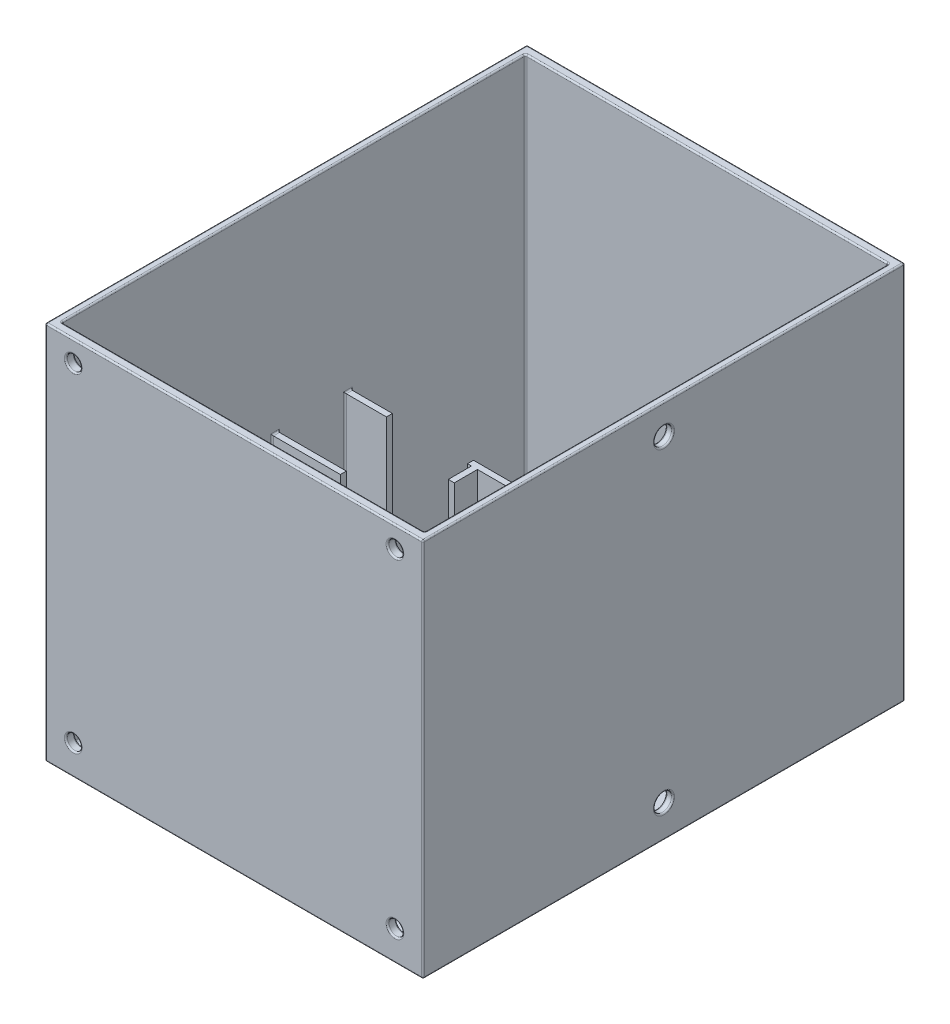
SolidWorks part; units mm, degrees
ref_plane "前视基准面" through (0, 0, 0) normal (0, 0, 1) x (1, 0, 0)
ref_plane "上视基准面" through (0, 0, 0) normal (0, 1, 0) x (1, 0, 0)
ref_plane "右视基准面" through (0, 0, 0) normal (1, 0, 0) x (0, 0, -1)
sketch "草图2" plane through (0, 0, 0) normal (0, 0, 1) x (1, 0, 0)
  line L0 (-53.75, 54.9) -> (53.75, 54.9)
  line L1 (-60.6355, -61.9328) -> (60.6355, -61.9328)
  line L2 (-60.6355, -61.9328) -> (-60.6355, 61.9328)
  line L3 (-60.6355, 61.9328) -> (60.6355, 61.9328)
  line L4 (60.6355, -61.9328) -> (60.6355, 61.9328)
  line L5 (-60.6355, -61.9328) -> (60.6355, 61.9328) construction
  line L6 (-60.6355, 61.9328) -> (60.6355, -61.9328) construction
  line L7 (53.75, 54.9) -> (53.75, -54.9)
  line L8 (53.75, -54.9) -> (-53.75, -54.9)
  line L9 (-53.75, -54.9) -> (-53.75, 54.9)
  circle A0 centre (-53.75, 54.9) radius 2.4552
  circle A1 centre (-53.75, -54.9) radius 2.4552
  circle A2 centre (53.75, 54.9) radius 2.4552
  circle A3 centre (53.75, -54.9) radius 2.4552
  point P0 (0, 0)
  dimension "D1" = 107.5
  dimension "D2" = 54.9
  dimension "D3" = 109.8
  dimension "D4" = 53.75
extrude "凸台-拉伸2" add sketch "草图2" along normal blind 3 contours L1 L4 L3 L2 A3 L8 A1 L9 A0 L0 A2 L7 | A3 L7 A2 L0 A0 L9 A1 L8
sketch "草图4" plane through (0, 0, 0) normal (0, 0, -1) x (-1, 0, 0)
  line L0 (-60.6355, 61.9328) -> (-60.6355, -61.9328)
  line L1 (-60.6355, -61.9328) -> (-63.1355, -61.9328)
  line L2 (-63.1355, -61.9328) -> (-63.1355, 61.9328)
  line L3 (-63.1355, 61.9328) -> (-60.6355, 61.9328)
  dimension "D1" = 2.5
extrude "凸台-拉伸3" add sketch "草图4" along normal blind 155 and the other way blind 3
sketch "草图5" plane through (0, 0, 0) normal (0, 0, -1) x (-1, 0, 0)
  line L0 (60.6355, 61.9328) -> (63.1355, 61.9328)
  line L1 (63.1355, 61.9328) -> (63.1355, -61.9328)
  line L2 (63.1355, -61.9328) -> (60.6355, -61.9328)
  line L3 (60.6355, -61.9328) -> (60.6355, 61.9328)
  dimension "D1" = 2.5
extrude "凸台-拉伸4" add sketch "草图5" along normal blind 155 and the other way blind 3
sketch "草图6" plane through (0, 0, -155) normal (0, 0, -1) x (-1, 0, 0)
  line L1 (-63.1355, 61.9328) -> (63.1355, 61.9328)
  line L2 (-63.1355, 61.9328) -> (-63.1355, -61.9328)
  line L3 (-63.1355, -61.9328) -> (63.1355, -61.9328)
  line L4 (63.1355, 61.9328) -> (63.1355, -61.9328)
extrude "凸台-拉伸5" add sketch "草图6" along normal blind 3
sketch "草图8" plane through (0, -61.9328, 0) normal (0, -1, 0) x (1, 0, 0)
  line L1 (-63.1355, 3) -> (63.1355, 3)
  line L2 (-63.1355, 3) -> (-63.1355, -158)
  line L3 (-63.1355, -158) -> (63.1355, -158)
  line L4 (63.1355, 3) -> (63.1355, -158)
extrude "凸台-拉伸6" add sketch "草图8" along normal blind 3
sketch "草图9" plane through (0, -61.9328, 0) normal (0, 1, 0) x (1, 0, 0)
  line L0 (-60.6355, 0) -> (-60.6355, 49.6525)
  line L1 (-60.6355, 0) -> (-60.6355, 155) construction
  line L2 (-60.6355, 49.6525) -> (60.6355, 49.6525)
  line L3 (60.6355, 0) -> (60.6355, 155) construction
  line L4 (60.6355, 49.6525) -> (60.6355, 47.6525)
  line L5 (60.6355, 47.6525) -> (-60.6355, 47.6525)
  line M3 (60.6355, 0) -> (60.6355, 155)
  line M5 (-60.6355, 155) -> (-60.6355, 0)
  dimension "D1" = 2
extrude "凸台-拉伸7" add sketch "草图9" along normal blind 56 contours L5 L2 M3 M5
sketch "草图10" plane through (0, -61.9328, 0) normal (0, 1, 0) x (1, 0, 0)
  line L0 (0, 0) -> (0, 47.6525)
  line L1 (-1.3526, 7) -> (-1.3526, 0)
  line L2 (-60.6355, 0) -> (60.6355, 0) construction
  line L3 (60.6355, 47.6525) -> (-60.6355, 47.6525) construction
  line L4 (-3.9159, 47.6525) -> (-3.9159, 42.9086)
  line L5 (-3.9159, 42.9086) -> (-1.9159, 42.9086)
  line L6 (-1.9159, 42.9086) -> (-1.9159, 47.6525)
  line L7 (60.6355, 47.6525) -> (-60.6355, 47.6525) construction
  line L8 (-1.9159, 47.6525) -> (-3.9159, 47.6525)
  line L9 (-1.3526, 7) -> (-4.4792, 7)
  line L10 (-4.4792, 7) -> (-4.4792, 0)
  line L11 (-60.6355, 0) -> (60.6355, 0) construction
  line L12 (-1.3526, 0) -> (-4.4792, 0)
  line L13 (-2.9159, 42.9086) -> (-2.9159, 7)
  line L14 (-28.9159, 47.6525) -> (-28.9159, 43)
  line L15 (-28.9159, 43) -> (-30.9159, 43)
  line L16 (-30.9159, 43) -> (-30.9159, 47.6525)
  line L17 (-30.9159, 47.6525) -> (-28.9159, 47.6525)
  line L18 (23.0841, 47.6525) -> (23.0841, 42.9086)
  line L19 (23.0841, 42.9086) -> (25.0841, 42.9086)
  line L20 (25.0841, 42.9086) -> (25.0841, 47.6525)
  line L21 (25.0841, 47.6525) -> (23.0841, 47.6525)
  line L22 (23.0841, 0) -> (23.0841, 7)
  line L23 (23.0841, 7) -> (25.1289, 7)
  line L24 (25.1289, 7) -> (25.1289, 0)
  line L25 (25.1289, 0) -> (23.0841, 0)
  line L26 (-28.9159, 0) -> (-30.9159, 0)
  line L27 (-30.9159, 0) -> (-30.9159, 7)
  line L28 (-30.9159, 7) -> (-28.9159, 7)
  line L29 (-28.9159, 7) -> (-28.9159, 0)
  line M9 (60.6355, 47.6525) -> (-60.6355, 47.6525)
  line M11 (-60.6355, 0) -> (60.6355, 0)
  dimension "D1" = 36
  dimension "D2" = 7
  dimension "D3" = 2
  dimension "D4" = 2
  dimension "D5" = 25
  dimension "D6" = 25
  dimension "D7" = 2
extrude "凸台-拉伸9" add sketch "草图10" along normal blind 56 contours L16 L15 L14 M9 | L29 L28 L27 M11 | L9 L10 L1 M11 | L5 L6 L4 M9 | L24 L23 L22 M11 | L18 L19 L20 L21
sketch "草图11" plane through (0, -61.9328, 0) normal (0, 1, 0) x (1, 0, 0)
  line L0 (-60.6355, 49.6525) -> (-60.6355, 94.6525)
  line L1 (-60.6355, 0) -> (-60.6355, 155) construction
  line L2 (-60.6355, 94.6525) -> (60.6355, 94.6525)
  line L3 (60.6355, 49.6525) -> (60.6355, 155) construction
  line L4 (60.6355, 94.6525) -> (60.6355, 49.6525)
  line L5 (60.6355, 49.6525) -> (-60.6355, 49.6525)
  line L6 (0, 49.6525) -> (0, 94.6525)
  line L7 (-1, 94.6525) -> (-1, 86.9025)
  line L8 (-1, 86.9025) -> (1, 86.9025)
  line L9 (1, 86.9025) -> (1, 94.6525)
  line L10 (-1, 49.6525) -> (-1, 58.4025)
  line L11 (-1, 58.4025) -> (1, 58.4025)
  line L12 (1, 58.4025) -> (1, 49.6525)
  line L13 (-16.3327, 94.6525) -> (-16.3327, 86.9025)
  line L14 (-16.3327, 86.9025) -> (-18.3327, 86.9025)
  line L15 (-18.3327, 86.9025) -> (-18.3327, 94.6525)
  line L16 (-18.3327, 49.6525) -> (-18.3327, 58.4025)
  line L17 (-18.3327, 58.4025) -> (-16.3327, 58.4025)
  line L18 (-16.3327, 58.4025) -> (-16.3327, 49.6525)
  line L19 (14.2318, 94.6525) -> (14.2318, 86.9025)
  line L20 (14.2318, 86.9025) -> (16.2318, 86.9025)
  line L21 (16.2318, 86.9025) -> (16.2318, 94.6525)
  line L22 (14.2318, 49.6525) -> (14.2318, 58.4025)
  line L23 (14.2318, 58.4025) -> (16.2318, 58.4025)
  line L24 (16.2318, 58.4025) -> (16.2318, 49.6525)
  line L25 (16.2318, 49.6525) -> (14.2318, 49.6525)
  line L26 (-17.8539, 94.6525) -> (-16.3327, 94.6525)
  line L27 (-1, 94.6525) -> (1, 94.6525)
  line L28 (14.2318, 94.6525) -> (16.2318, 94.6525)
  line L29 (16.2318, 49.6525) -> (14.2318, 49.6525)
  line L30 (1, 49.6525) -> (-1, 49.6525)
  line L31 (-16.3327, 49.6525) -> (-18.3327, 49.6525)
  dimension "D1" = 45
  dimension "D2" = 2
  dimension "D3" = 1
  dimension "D4" = 28.5
  dimension "D5" = 7.75
  dimension "D6" = 2
  dimension "D7" = 8.75
  dimension "D8" = 7.75
  dimension "D9" = 2
  dimension "D10" = 2
  dimension "D11" = 2
  dimension "D12" = 8.75
  dimension "D13" = 8.75
  dimension "D14" = 7.75
extrude "凸台-拉伸10" add sketch "草图11" along normal blind 56 contours L15 L14 L13 L2 | L18 L17 L16 L5 | L20 L21 L2 L19 | L24 L23 L22 L5 | L10 L11 L12 L30 | L7 L8 L9 L27
sketch "草图14" plane through (0, -61.9328, 0) normal (0, 1, 0) x (1, 0, 0)
  line L0 (-60.6355, 94.6525) -> (60.6355, 94.6525)
  line L1 (-60.6355, 49.6525) -> (-60.6355, 155) construction
  line L2 (60.6355, 49.6525) -> (60.6355, 155) construction
  line L3 (60.6355, 94.6525) -> (60.6355, 96.6525)
  line L4 (60.6355, 96.6525) -> (-60.6355, 96.6525)
  line L5 (-60.6355, 96.6525) -> (-60.6355, 94.6525)
  line L6 (16.2318, 86.9025) -> (-60.6355, 86.9025)
  line L7 (16.2318, 58.4025) -> (-60.6355, 57.7713)
  line L8 (-60.6355, 0) -> (-60.6355, 155) construction
  line L9 (-60.6355, 72.281) -> (-37.7682, 72.281)
  line L10 (-37.7682, 72.281) -> (-37.7682, 70.281)
  line L11 (-37.7682, 70.281) -> (-60.6355, 70.281)
  line L12 (-60.6355, 70.281) -> (-60.6355, 72.281)
  line L13 (60.6355, 70.281) -> (60.6355, 72.4025)
  line L14 (60.6355, 0) -> (60.6355, 155) construction
  line L15 (60.6355, 72.4025) -> (48.2318, 72.4025)
  line L16 (48.2318, 72.4025) -> (48.2318, 70.281)
  line L17 (48.2318, 70.281) -> (60.6355, 70.281)
  point P28 (32.2993, 70.0615)
  dimension "D1" = 54
  dimension "D2" = 86
extrude "凸台-拉伸11" add sketch "草图14" along normal blind 56 contours L4 L5 L0 L3 | L12 L11 L10 L9 | L16 L17 L13 L15
sketch "草图15" plane through (0, -61.9328, 0) normal (0, 1, 0) x (1, 0, 0)
  line L0 (-41.2643, 96.6525) -> (-41.2643, 94.6525)
  line L1 (60.6355, 96.6525) -> (-60.6355, 96.6525) construction
  line L2 (-41.2643, 96.6525) -> (-19.6592, 96.6525)
  line L3 (-19.6592, 96.6525) -> (-19.6592, 94.6525)
  line L4 (-19.6592, 94.6525) -> (-41.2643, 94.6525)
  line L5 (-60.6355, 94.6525) -> (-18.3327, 94.6525) construction
  line L6 (-41.2643, 96.6525) -> (-19.6592, 96.6525)
  circle A0 centre (-30.4618, 124.8263) radius 30.1737
  line M2 (-60.6355, 96.6525) -> (60.6355, 96.6525)
extrude "切除-拉伸3" cut sketch "草图15" along normal blind 56 contours A0 M2 | A0 L0 L4 | A0 L4 L3
sketch "草图16" plane through (0, -61.9328, 0) normal (0, 1, 0) x (1, 0, 0)
  line L0 (-41.2643, 96.6525) -> (-41.2643, 94.6525)
  line L1 (-60.6355, 94.6525) -> (-41.2643, 94.6525) construction
  line L2 (-41.2643, 96.6525) -> (-41.2643, 94.6525) construction
  line L3 (-41.2643, 94.6525) -> (-46.7552, 94.6525)
  line L4 (-46.7552, 94.6525) -> (-46.7552, 96.6525)
  line L5 (-41.2643, 96.6525) -> (-60.6355, 96.6525) construction
  line L6 (-46.7552, 96.6525) -> (-41.2643, 96.6525)
extrude "切除-拉伸4" cut sketch "草图16" along normal blind 56
sketch "草图17" plane through (63.1355, 0, 0) normal (1, 0, 0) x (0, 0, -1)
  line L0 (-3, -2.5408) -> (158, -2.5408)
  line L1 (-3, 61.9328) -> (-3, -64.9328) construction
  line L2 (158, 61.9328) -> (158, -64.9328) construction
  line L3 (77.5, 61.9328) -> (77.5, -2.5408)
  line L4 (-3, 61.9328) -> (158, 61.9328) construction
  line L5 (77.5, -2.5408) -> (77.5, -64.9328)
  line L6 (158, -64.9328) -> (-3, -64.9328) construction
  line L7 (77.5, 51.9328) -> (77.5, -54.0672)
  circle A0 centre (77.5, 51.9328) radius 3
  circle A1 centre (77.5, -54.0672) radius 3
  dimension "D1" = 106
  dimension "D2" = 10
extrude "切除-拉伸5" cut sketch "草图17" against normal blind 56 contours L3 A0 | L3 A0 | L5 A1 L7 | L7 A1 L5
fillet "圆角2" radius 0.5 72 edges at (-60.6355, 0, 0) (0, 61.9328, 0) (60.6355, 0, 0) (-16.6976, -61.9328, 0) (-28.9159, -33.9328, 0) (-30.9159, -33.9328, 0) (-45.7757, -61.9328, 0) (-29.9159, -5.9328, 0) (56.2052, -54.9, 0) (10.8657, -61.9328, 0) (56.2052, 54.9, 0) (-4.4792, -33.9328, 0) (-1.3526, -33.9328, 0) (-2.9159, -5.9328, 0) (-51.2948, 54.9, 0) (-51.2948, -54.9, 0) (-51.2948, 54.9, 3) (42.8822, -61.9328, 0) (25.1289, -33.9328, 0) (23.0841, -33.9328, 0) (24.1065, -5.9328, 0) (56.2052, 54.9, 3) (-60.6355, -61.9328, -125.8263) (60.6355, -61.9328, -125.8263) (56.2052, -54.9, 3) (-60.6355, -33.9328, -94.6525) (60.6355, -33.9328, -96.6525) (-60.6355, -33.9328, -96.6525) (60.6355, -33.9328, -94.6525) (-60.6355, -5.9328, -95.6525) (60.6355, -5.9328, -95.6525) (-60.6355, -61.9328, -83.4667) (-60.6355, -5.9328, -71.281) (-60.6355, -33.9328, -72.281) (-60.6355, -33.9328, -70.281) (60.6355, -61.9328, -83.5275) (60.6355, -33.9328, -70.281) (60.6355, -33.9328, -72.4025) (60.6355, -5.9328, -71.3417) (63.1355, 61.9328, -77.5) (60.6355, 61.9328, -77.5) (60.6355, -61.9328, -23.8263) (63.1355, -1.5, 3) (60.6355, 0, -155) (60.6355, 48.9328, -77.5) (63.1355, 51.9328, -80.5) (60.6355, -57.0672, -77.5) (63.1355, -54.0672, -80.5) (0, 61.9328, 3) (-60.6355, -61.9328, -23.8263) (-60.6355, 61.9328, -77.5) (-63.1355, 61.9328, -77.5) (-63.1355, -1.5, 3) (-60.6355, 0, -155) (0, -61.9328, -155) (0, 61.9328, -155) (63.1355, -1.5, -158) (-63.1355, -1.5, -158) (0, 61.9328, -158) (-63.1355, -64.9328, -77.5) (0, -64.9328, -158) (63.1355, -64.9328, -77.5) (0, -64.9328, 3) (60.6355, -61.9328, -59.9667) (-60.6355, -61.9328, -59.9667) (-51.2948, -54.9, 3) (-60.6355, -33.9328, -47.6525) (60.6355, -33.9328, -47.6525) (60.6355, -33.9328, -49.6525) (-60.6355, -33.9328, -49.6525) (60.6355, -5.9328, -48.6525) (-60.6355, -5.9328, -48.6525)
sketch "草图18" plane through (63.1355, 0, 0) normal (1, 0, 0) x (0, 0, -1)
  line L0 (77.5, 48.4328) -> (77.5, -50.5672)
  circle A0 centre (77.5, 51.9328) radius 3.5 construction
  circle A1 centre (77.5, -54.0672) radius 3.5 construction
  dimension "D1" = 99
